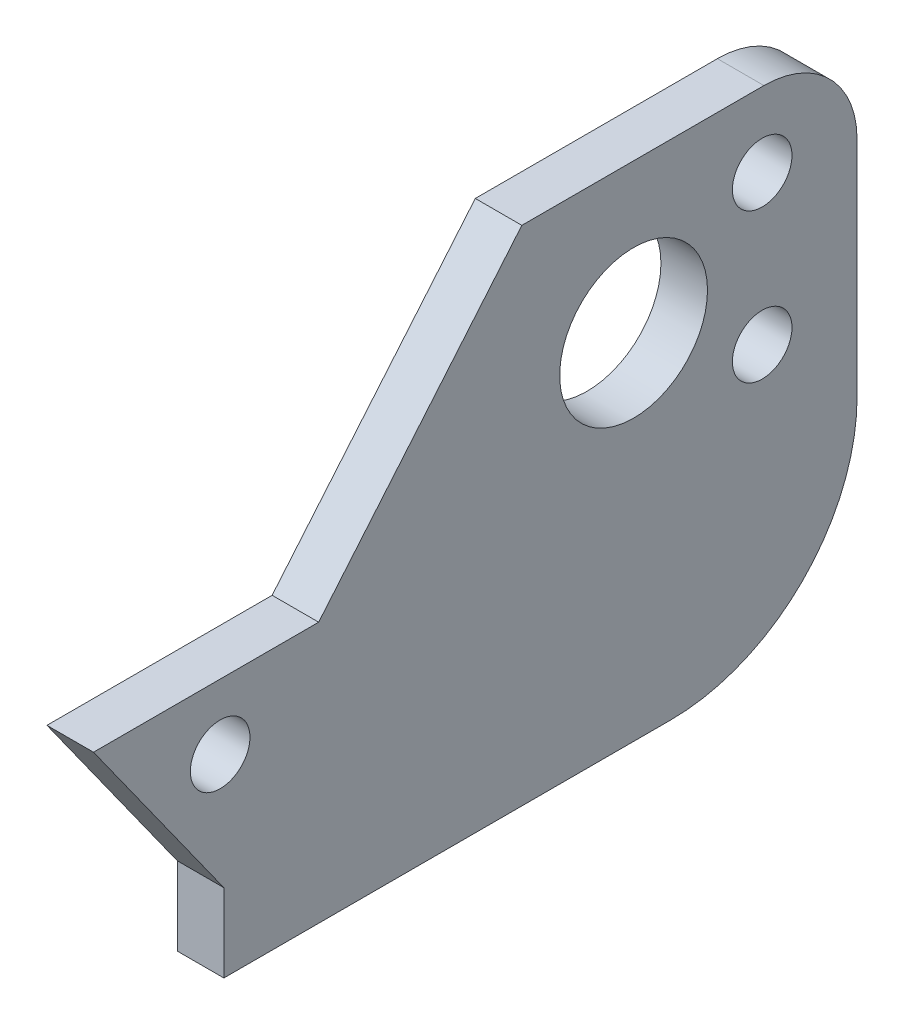
SolidWorks part; units mm, degrees
material "Plain Carbon Steel"
ref_plane "Front Plane" through (0, 0, 0) normal (0, 0, 1) x (1, 0, 0)
ref_plane "Top Plane" through (0, 0, 0) normal (0, 1, 0) x (1, 0, 0)
ref_plane "Right Plane" through (0, 0, 0) normal (1, 0, 0) x (0, 0, -1)
sketch "Sketch1" plane through (0, 0, 0) normal (1, 0, 0) x (0, 0, -1)
  line L0 (-45.1764, 3.0469) -> (-38.7478, -5.9531)
  line L1 (-36.7135, -7) -> (0, -7)
  line L3 (-43.142, 7) -> (0, 7)
  line L4 (0, -7) -> (0, 7)
  line L6 (-18, 20) -> (0, 20)
  line L7 (0, 20) -> (0, 7)
  line L8 (-18, 20) -> (-28.9083, 7)
  arc A2 (-38.7478, -5.9531) -> (-36.7135, -7) centre (-36.7135, -4.5) ccw
  arc A3 (-45.1764, 3.0469) -> (-43.142, 7) centre (-43.142, 4.5) cw
  point P0 (0, 0)
  point P2 (0, 0)
  point P11 (0, 7)
  point P14 (-38, -7)
  point P17 (-48, 7)
  dimension "D4" = 2.5
  dimension "D1" = 14
  dimension "D2" = 48
  dimension "D3" = 10
  dimension "D6" = 27
  dimension "D7" = 18
  dimension "D8" = 50
extrude "Boss-Extrude1" add sketch "Sketch1" along normal mid plane 18 contours L7 L6 L3 | A3 L0 A2 L1 L4 L3 region at (0, 0.2232, 21.3727) region at (0, 12.9962, 11.9385)
ref_plane "Plane1" through (0, 0, 0) normal (1, 0, 0) x (0, 0, -1)
sketch "Sketch5" plane through (0, 0, 0) normal (1, 0, 0) x (0, 0, -1)
  line L0 (0, 20) -> (0, -7) construction
  line L1 (-18, 20) -> (0, 20) construction
  line L5 (-30.5, -8) -> (6.5, -8)
  line L6 (-30.5, -8) -> (-30.5, 32)
  line L7 (-30.5, 32) -> (6.5, 32)
  line L8 (6.5, -8) -> (6.5, 32)
  line L9 (-30.5, -8) -> (6.5, 32) construction
  line L10 (-30.5, 32) -> (6.5, -8) construction
  circle A0 centre (-12, 12) radius 3.9687
  dimension "D1" = 7.9375
  dimension "D2" = 12
  dimension "D3" = 37
  dimension "D4" = 8
  dimension "D5" = 40
extrude "Cut-Extrude4" cut sketch "Sketch5" along normal mid plane 13 contours L5 L8 L7 L6 | A0 region at (0, 12, 29.9551)
extrude "Cut-Extrude5" cut sketch "Sketch5<3>" against normal mid plane 25 contours A0
sketch "Sketch5<3>" plane through (0, 0, 0) normal (1, 0, 0) x (0, 0, -1) same geometry as "Sketch5"
fillet "Fillet2" radius 5 1 edges at (-7.75, 20, 0)
sketch "Sketch8" plane through (-9, 0, 0) normal (-1, 0, 0) x (0, 0, 1)
  line L2 (38, -7) -> (48, 7)
  line L4 (48, 7) -> (41, 7)
  line L5 (43.142, 7) -> (28.9083, 7) construction
  line L6 (41, 7) -> (34, -2.8)
  line L7 (34, -2.8) -> (34, -7)
  line L8 (36.7135, -7) -> (0, -7) construction
  line L9 (34, -7) -> (38, -7)
  line L10 (45.1764, 3.0469) -> (38.7478, -5.9531) construction
  dimension "D1" = 7
  dimension "D2" = 4
sketch "Sketch9" plane through (-9, 0, 0) normal (1, 0, 0) x (0, 0, -1)
  line L0 (-5.0949, 16) -> (-5.0949, 8) construction
  arc A1 (-5.0949, 8) -> (-5.0949, 16) centre (-12, 12) ccw
  circle A13 centre (-12, 12) radius 3.9687 construction
  point P5 (-5.0949, 8)
  point P25 (-5.0949, 16)
  dimension "D1" = 7.98
  dimension "D2" = 8
fillet "Fillet3" radius 10 1 edges at (-7.75, -7, 0)
sketch "Sketch12" plane through (0, 0, 0) normal (1, 0, 0) x (0, 0, -1)
  line L0 (-43.142, 7) -> (-28.9083, 7) construction
  line L1 (-48.4083, -8) -> (1.5917, -8)
  line L2 (-48.4083, -8) -> (-48.4083, 22)
  line L3 (-48.4083, 22) -> (1.5917, 22)
  line L4 (1.5917, -8) -> (1.5917, 22)
  line L5 (-48.4083, -8) -> (1.5917, 22) construction
  line L6 (-48.4083, 22) -> (1.5917, -8) construction
  point P0 (-23.4083, 7)
  dimension "D1" = 50
  dimension "D2" = 30
  dimension "D3" = 5.5
extrude "Cut-Extrude12" cut sketch "Sketch12" against normal up to surface (6.5 mm away) and the other way through all up to face at (-6.5, 12, 8.0312)
extrude "Cut-Extrude13" cut sketch "Sketch8" against normal through all
hole_wizard "M3 Clearance Hole1" positions "Sketch9" profile "Sketch13" hole size "M3" standard "ANSI Metric"
sketch "Sketch13" plane through (-9, 16, 5.0949) normal (0, 1, 0) x (0, 0, 1)
  line L0 (0, 0) -> (0, 3.4614)
  line L1 (0, 3.4614) -> (1.6, 2.5)
  line L2 (1.6, 2.5) -> (1.6, 0)
  line L5 (1.6, 0) -> (0, 0)
  line L10 (0, 3.4614) -> (-1.6, 2.5) construction
  line L11 (0, -6.35) -> (0, 107.95) construction
  dimension "Hole Dia." = 3.2
  dimension "Hole Depth" = 2.5
  dimension "Drill Angle" = 118
sketch "Sketch14" plane through (-9, 0, 0) normal (-1, 0, 0) x (0, 0, 1)
  line L0 (34.1988, 3.5) -> (37.0469, 1.4657) construction
  line L1 (41, 7) -> (34, -2.8) construction
  line L2 (34.1988, 3.5) -> (34.1988, 7) construction
  line L3 (41, 7) -> (28.9083, 7) construction
  point P0 (34.1988, 3.5)
  dimension "D1" = 3.5
hole_wizard "M3 Clearance Hole2" positions "Sketch14" profile "Sketch15" hole size "M3" standard "ANSI Metric"
sketch "Sketch15" plane through (-9, 3.5, 34.1988) normal (0, 1, 0) x (0, 0, 1)
  line L0 (0, 0) -> (0, 3.4614)
  line L1 (0, 3.4614) -> (1.6, 2.5)
  line L2 (1.6, 2.5) -> (1.6, 0)
  line L5 (1.6, 0) -> (0, 0)
  line L10 (0, 3.4614) -> (-1.6, 2.5) construction
  line L11 (0, -6.35) -> (0, 107.95) construction
  dimension "Hole Dia." = 3.2
  dimension "Hole Depth" = 2.5
  dimension "Drill Angle" = 118
